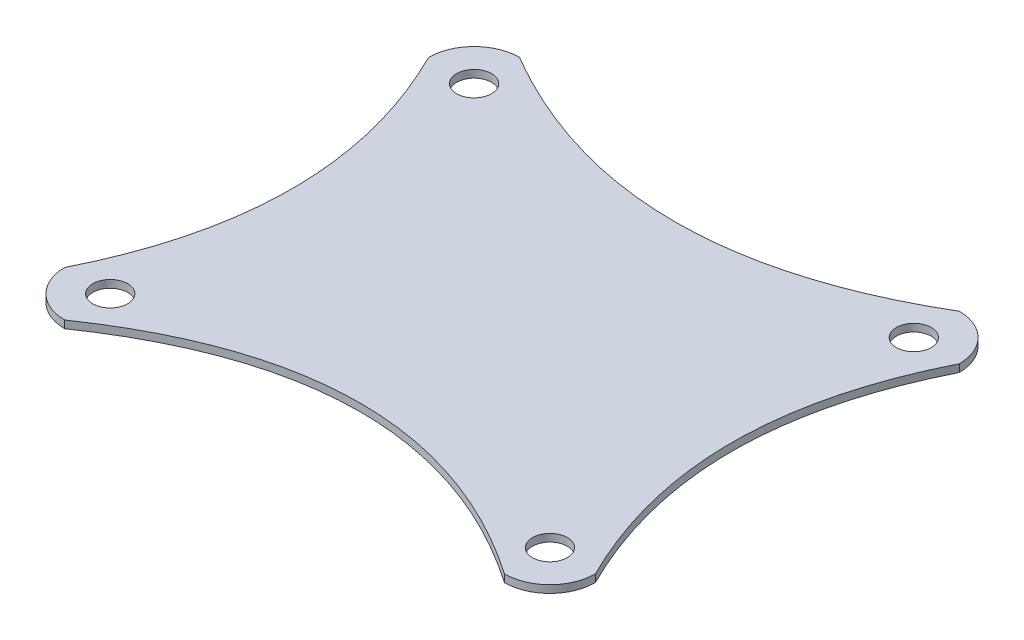
SolidWorks part; units mm, degrees
material "Plain Carbon Steel"
ref_plane "Front Plane" through (0, 0, 0) normal (0, 0, 1) x (1, 0, 0)
ref_plane "Top Plane" through (0, 0, 0) normal (0, 1, 0) x (1, 0, 0)
ref_plane "Right Plane" through (0, 0, 0) normal (1, 0, 0) x (0, 0, -1)
sketch "Sketch1" plane through (0, -8.1692, 0) normal (0, -1, 0) x (1, 0, 0)
  line L5 (-62.7825, 37.126) -> (-27.7825, 7.126) construction
  line L6 (-62.7825, 7.126) -> (-27.7825, 37.126) construction
  arc A0 (-30.7825, 37.126) -> (-27.7825, 34.126) centre (-30.7825, 34.126) cw
  arc A1 (-30.7825, 7.126) -> (-27.7825, 10.126) centre (-30.7825, 10.126) ccw
  arc A2 (-62.7825, 10.126) -> (-59.7825, 7.126) centre (-59.7825, 10.126) ccw
  arc A3 (-59.7825, 37.126) -> (-62.7825, 34.126) centre (-59.7825, 34.126) ccw
  circle A4 centre (-59.7825, 34.126) radius 1.15
  circle A5 centre (-30.7825, 34.126) radius 1.15
  circle A6 centre (-30.7825, 10.126) radius 1.15
  circle A7 centre (-59.7825, 10.126) radius 1.15
  spline S0 degree 2 poles (-59.7825, 37.126) (-45.2825, 27.126) (-30.7825, 37.126) knots 0 0 0 1 1 1
  spline S1 degree 2 poles (-59.7825, 7.126) (-45.2825, 15.6661) (-30.7825, 7.126) knots 0 0 0 1 1 1
  spline S2 degree 2 poles (-62.7825, 34.126) (-56.7825, 22.126) (-62.7825, 10.126) knots 0 0 0 1 1 1
  spline S3 degree 2 poles (-27.7825, 34.126) (-33.7825, 22.126) (-27.7825, 10.126) knots 0 0 0 1 1 1
  point P0 (-45.2825, 22.126)
  dimension "D3" = 3
  dimension "D4" = 2.3
  dimension "D1" = 30
  dimension "D2" = 35
extrude "Boss-Extrude1" add sketch "Sketch1" along a picked direction on the side of the normal blind 1
sketch "Sketch2" plane through (0, -8.1692, 0) normal (0, 1, 0) x (1, 0, 0)
  arc A8 (-62.7825, -34.126) -> (-59.7825, -37.126) centre (-59.7825, -34.126) ccw
  arc A9 (-30.7825, -37.126) -> (-27.7825, -34.126) centre (-30.7825, -34.126) ccw
  arc A10 (-27.7825, -10.126) -> (-30.7825, -7.126) centre (-30.7825, -10.126) ccw
  arc A11 (-59.7825, -7.126) -> (-62.7825, -10.126) centre (-59.7825, -10.126) ccw
  arc A12 (-62.7825, -34.126) -> (-59.7825, -37.126) centre (-59.7825, -34.126) ccw
  arc A13 (-30.7825, -37.126) -> (-27.7825, -34.126) centre (-30.7825, -34.126) ccw
  arc A14 (-27.7825, -10.126) -> (-30.7825, -7.126) centre (-30.7825, -10.126) ccw
  arc A15 (-59.7825, -7.126) -> (-62.7825, -10.126) centre (-59.7825, -10.126) ccw
  parabola Q8 (-59.7825, -37.126) -> (-30.7825, -37.126) focus (-45.2825, -42.6385) apex (-45.2825, -32.126)
  parabola Q9 (-27.7825, -34.126) -> (-27.7825, -10.126) focus (-18.7825, -22.126) apex (-30.7825, -22.126)
  parabola Q10 (-30.7825, -7.126) -> (-59.7825, -7.126) focus (-45.2825, 0.9135) apex (-45.2825, -11.396)
  parabola Q11 (-62.7825, -10.126) -> (-62.7825, -34.126) focus (-71.7825, -22.126) apex (-59.7825, -22.126)
  parabola Q12 (-59.7825, -37.126) -> (-30.7825, -37.126) focus (-45.2825, -42.6385) apex (-45.2825, -32.126)
  parabola Q13 (-27.7825, -34.126) -> (-27.7825, -10.126) focus (-18.7825, -22.126) apex (-30.7825, -22.126)
  parabola Q14 (-30.7825, -7.126) -> (-59.7825, -7.126) focus (-45.2825, 0.9135) apex (-45.2825, -11.396)
  parabola Q15 (-62.7825, -10.126) -> (-62.7825, -34.126) focus (-71.7825, -22.126) apex (-59.7825, -22.126)
  dimension "D1" = 0
extrude "Cut-Extrude1" cut sketch "Sketch2" against normal blind 0.5 contours A12 Q12 A13 Q13 A14 Q14 A15 Q15
sketch "Sketch3" plane through (0, -8.6692, 0) normal (0, 1, 0) x (1, 0, 0)
  circle A2 centre (-45.2825, -22.126) radius 5.7627
extrude "Boss-Extrude2" add sketch "Sketch3" along normal blind 1
ref_plane "Plane1" through (0, 0, 22.126) normal (0, 0, 1) x (1, 0, 0)
sketch "Sketch5" plane through (0, 0, 22.126) normal (0, 0, 1) x (1, 0, 0)
  line L0 (-45.2825, -3.9692) -> (-45.2825, -1.5757) construction
  circle A0 centre (-50.3321, -7.6692) radius 0.5
revolve "Cut-Revolve1" cut sketch "Sketch5" angle 360 about L0
fillet "Fillet1" radius 0.5 2 edges at (-50.8321, -7.6692, 22.126) (-40.7329, -7.6692, 22.126)
fillet "Fillet2" radius 0.1 1 edges at (-51.0452, -7.6692, 22.126)
fillet "Fillet3" radius 0.5 1 edges at (-51.0452, -8.6692, 22.126)
sketch "Sketch6" plane through (0, -7.6692, 0) normal (0, 1, 0) x (1, 0, 0)
  circle A0 centre (-45.2825, -22.126) radius 3.5532
extrude "Cut-Extrude2" cut sketch "Sketch6" against normal blind 0.5
fillet "Fillet4" radius 0.5 1 edges at (-48.8357, -7.6692, 22.126)
move or copy body "Body-Move/Copy1" bodies to move or copy 105 copy no rotation origin (-45.2825, -8.4192, 0) rotation axis (0, 0, 1) rotation angle 180
